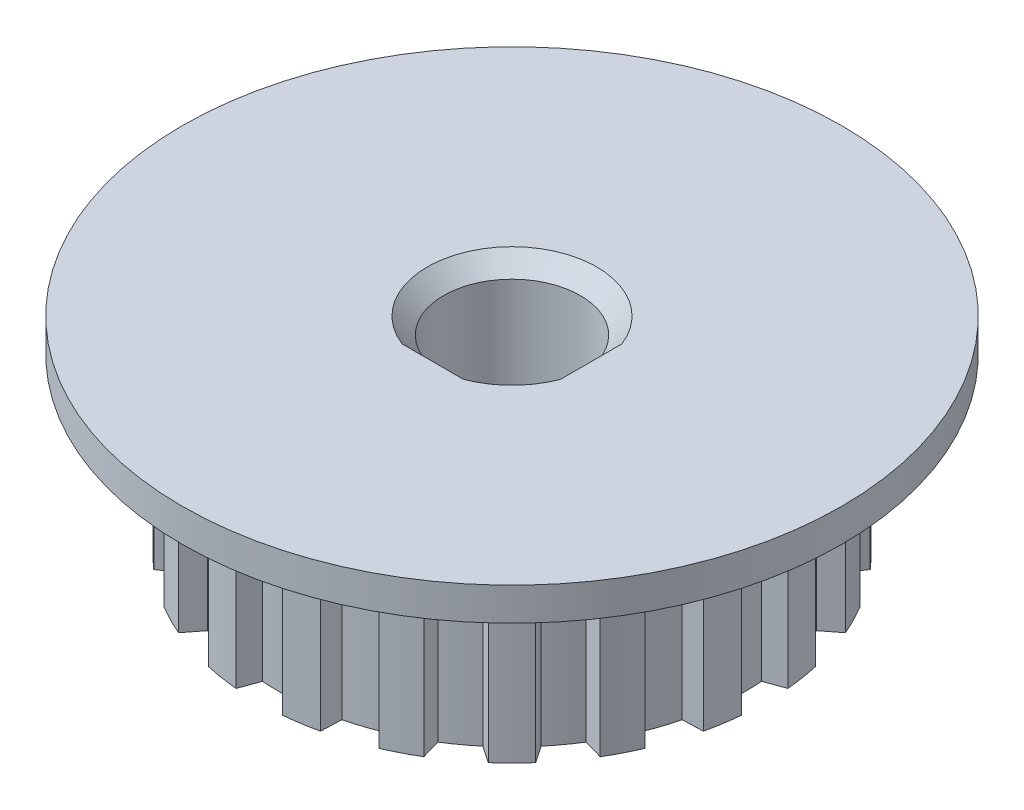
SolidWorks part; units mm, degrees
ref_plane "Спереди" through (0, 0, 0) normal (0, 0, 1) x (1, 0, 0)
ref_plane "Сверху" through (0, 0, 0) normal (0, 1, 0) x (1, 0, 0)
ref_plane "Справа" through (0, 0, 0) normal (1, 0, 0) x (0, 0, -1)
sketch "Эскиз2" plane through (0, 0, 0) normal (0, 1, 0) x (1, 0, 0)
  line L0 (0, 0) -> (0, 16.4) construction
  line L1 (0, 0) -> (2.5655, 16.1981) construction
  line L2 (0, 0) -> (-2.5655, 16.1981) construction
  line L3 (-0.975, 14.1665) -> (-1.4007, 15.3362)
  line L4 (0.975, 14.1665) -> (1.4007, 15.3362)
  line L5 (3.4504, 13.7744) -> (3.407, 15.0184)
  line L6 (5.305, 13.1718) -> (6.0713, 14.1527)
  line L7 (7.5381, 12.034) -> (7.8812, 13.2305)
  line L8 (9.1156, 10.8878) -> (10.1476, 11.5839)
  line L9 (10.8878, 9.1156) -> (11.5839, 10.1476)
  line L10 (12.034, 7.5381) -> (13.2305, 7.8812)
  line L11 (13.1718, 5.305) -> (14.1527, 6.0713)
  line L12 (13.7744, 3.4504) -> (15.0184, 3.407)
  line L13 (14.1665, 0.975) -> (15.3362, 1.4007)
  line L14 (14.1665, -0.975) -> (15.3362, -1.4007)
  line L15 (13.7744, -3.4504) -> (15.0184, -3.407)
  line L16 (13.1718, -5.305) -> (14.1527, -6.0713)
  line L17 (12.034, -7.5381) -> (13.2305, -7.8812)
  line L18 (10.8878, -9.1156) -> (11.5839, -10.1476)
  line L19 (9.1156, -10.8878) -> (10.1476, -11.5839)
  line L20 (7.5381, -12.034) -> (7.8812, -13.2305)
  line L21 (5.305, -13.1718) -> (6.0713, -14.1527)
  line L22 (3.4504, -13.7744) -> (3.407, -15.0184)
  line L23 (0.975, -14.1665) -> (1.4007, -15.3362)
  line L24 (-0.975, -14.1665) -> (-1.4007, -15.3362)
  line L25 (-3.4504, -13.7744) -> (-3.407, -15.0184)
  line L26 (-5.305, -13.1718) -> (-6.0713, -14.1527)
  line L27 (-7.5381, -12.034) -> (-7.8812, -13.2305)
  line L28 (-9.1156, -10.8878) -> (-10.1476, -11.5839)
  line L29 (-10.8878, -9.1156) -> (-11.5839, -10.1476)
  line L30 (-12.034, -7.5381) -> (-13.2305, -7.8812)
  line L31 (-13.1718, -5.305) -> (-14.1527, -6.0713)
  line L32 (-13.7744, -3.4504) -> (-15.0184, -3.407)
  line L33 (-14.1665, -0.975) -> (-15.3362, -1.4007)
  line L34 (-14.1665, 0.975) -> (-15.3362, 1.4007)
  line L35 (-13.7744, 3.4504) -> (-15.0184, 3.407)
  line L36 (-13.1718, 5.305) -> (-14.1527, 6.0713)
  line L37 (-12.034, 7.5381) -> (-13.2305, 7.8812)
  line L38 (-10.8878, 9.1156) -> (-11.5839, 10.1476)
  line L39 (-9.1156, 10.8878) -> (-10.1476, 11.5839)
  line L40 (-7.5381, 12.034) -> (-7.8812, 13.2305)
  line L41 (-5.305, 13.1718) -> (-6.0713, 14.1527)
  line L42 (-3.4504, 13.7744) -> (-3.407, 15.0184)
  circle A0 centre (0, 0) radius 16.4 construction
  circle A1 centre (0, 0) radius 15.9 construction
  circle A2 centre (0, 0) radius 15.4 construction
  circle A3 centre (0, 0) radius 14.2 construction
  arc A4 (-0.975, 14.1665) -> (0.975, 14.1665) centre (0, 0) cw
  arc A5 (3.4504, 13.7744) -> (5.305, 13.1718) centre (0, 0) cw
  arc A6 (7.5381, 12.034) -> (9.1156, 10.8878) centre (0, 0) cw
  arc A7 (10.8878, 9.1156) -> (12.034, 7.5381) centre (0, 0) cw
  arc A8 (13.1718, 5.305) -> (13.7744, 3.4504) centre (0, 0) cw
  arc A9 (14.1665, 0.975) -> (14.1665, -0.975) centre (0, 0) cw
  arc A10 (13.7744, -3.4504) -> (13.1718, -5.305) centre (0, 0) cw
  arc A11 (12.034, -7.5381) -> (10.8878, -9.1156) centre (0, 0) cw
  arc A12 (9.1156, -10.8878) -> (7.5381, -12.034) centre (0, 0) cw
  arc A13 (5.305, -13.1718) -> (3.4504, -13.7744) centre (0, 0) cw
  arc A14 (0.975, -14.1665) -> (-0.975, -14.1665) centre (0, 0) cw
  arc A15 (-3.4504, -13.7744) -> (-5.305, -13.1718) centre (0, 0) cw
  arc A16 (-7.5381, -12.034) -> (-9.1156, -10.8878) centre (0, 0) cw
  arc A17 (-10.8878, -9.1156) -> (-12.034, -7.5381) centre (0, 0) cw
  arc A18 (-13.1718, -5.305) -> (-13.7744, -3.4504) centre (0, 0) cw
  arc A19 (-14.1665, -0.975) -> (-14.1665, 0.975) centre (0, 0) cw
  arc A20 (-13.7744, 3.4504) -> (-13.1718, 5.305) centre (0, 0) cw
  arc A21 (-12.034, 7.5381) -> (-10.8878, 9.1156) centre (0, 0) cw
  arc A22 (-9.1156, 10.8878) -> (-7.5381, 12.034) centre (0, 0) cw
  arc A23 (-5.305, 13.1718) -> (-3.4504, 13.7744) centre (0, 0) cw
  arc A24 (-3.407, 15.0184) -> (-1.4007, 15.3362) centre (0, 0) cw
  arc A25 (1.4007, 15.3362) -> (3.407, 15.0184) centre (0, 0) cw
  arc A26 (6.0713, 14.1527) -> (7.8812, 13.2305) centre (0, 0) cw
  arc A27 (10.1476, 11.5839) -> (11.5839, 10.1476) centre (0, 0) cw
  arc A28 (13.2305, 7.8812) -> (14.1527, 6.0713) centre (0, 0) cw
  arc A29 (15.0184, 3.407) -> (15.3362, 1.4007) centre (0, 0) cw
  arc A30 (15.3362, -1.4007) -> (15.0184, -3.407) centre (0, 0) cw
  arc A31 (14.1527, -6.0713) -> (13.2305, -7.8812) centre (0, 0) cw
  arc A32 (11.5839, -10.1476) -> (10.1476, -11.5839) centre (0, 0) cw
  arc A33 (7.8812, -13.2305) -> (6.0713, -14.1527) centre (0, 0) cw
  arc A34 (3.407, -15.0184) -> (1.4007, -15.3362) centre (0, 0) cw
  arc A35 (-1.4007, -15.3362) -> (-3.407, -15.0184) centre (0, 0) cw
  arc A36 (-6.0713, -14.1527) -> (-7.8812, -13.2305) centre (0, 0) cw
  arc A37 (-10.1476, -11.5839) -> (-11.5839, -10.1476) centre (0, 0) cw
  arc A38 (-13.2305, -7.8812) -> (-14.1527, -6.0713) centre (0, 0) cw
  arc A39 (-15.0184, -3.407) -> (-15.3362, -1.4007) centre (0, 0) cw
  arc A40 (-15.3362, 1.4007) -> (-15.0184, 3.407) centre (0, 0) cw
  arc A41 (-14.1527, 6.0713) -> (-13.2305, 7.8812) centre (0, 0) cw
  arc A42 (-11.5839, 10.1476) -> (-10.1476, 11.5839) centre (0, 0) cw
  arc A43 (-7.8812, 13.2305) -> (-6.0713, 14.1527) centre (0, 0) cw
  point P11 (0, 14.2)
  dimension "D1" = 32.8
  dimension "D2" = 31.8
  dimension "D3" = 30.8
  dimension "D4" = 28.4
  dimension "D7" = 1.95
  dimension "D5" = 9
  dimension "D6" = 9
  dimension "D8" = 20
  dimension "D9" = 20
extrude "Вытянуть1" add sketch "Эскиз2" along normal blind 10.6
sketch "Эскиз3" plane through (0, 10.6, 0) normal (0, 1, 0) x (1, 0, 0)
  circle A0 centre (0, 0) radius 20
  dimension "D1" = 40
extrude "Вытянуть2" add sketch "Эскиз3" along normal blind 2
sketch "Эскиз5" plane through (0, 12.6, 0) normal (0, 1, 0) x (1, 0, 0)
  line L0 (3.8, -1.6681) -> (3.8, 1.6681)
  line L1 (1.6681, -3.8) -> (-1.6681, -3.8)
  circle A0 centre (0, 0) radius 4.15 construction
  arc A1 (1.6681, -3.8) -> (3.8, -1.6681) centre (0, 0) ccw
  arc A2 (-1.6681, -3.8) -> (3.8, 1.6681) centre (0, 0) cw
  dimension "D1" = 8.3
  dimension "D2" = 3.8
  dimension "D3" = 3.8
extrude "Вытянуть4" cut sketch "Эскиз5" against normal blind 10
sketch "Эскиз6" plane through (0, 0, 0) normal (0, -1, 0) x (1, 0, 0)
  circle A0 centre (0, 0) radius 4.15
  dimension "D1" = 8.3
extrude "Вытянуть5" cut sketch "Эскиз6" against normal up to surface (2.6 mm away) up to face at (0.95, 2.6, 0.95)
chamfer "Фаска1" distance 1 angle 45 4 edges at (3.8, 12.6, 0) (2.9345, 12.6, 2.9345) (0, 12.6, 3.8) (-2.9345, 12.6, -2.9345)
sketch "Эскиз7" plane through (0, 0, 0) normal (0, -1, 0) x (1, 0, 0)
  circle A0 centre (0, 0) radius 4.15
  circle A1 centre (0, 0) radius 7
  circle A2 centre (0, 0) radius 4.15 construction
  dimension "D1" = 14
extrude "Вытянуть6" add sketch "Эскиз7" along normal blind 2
